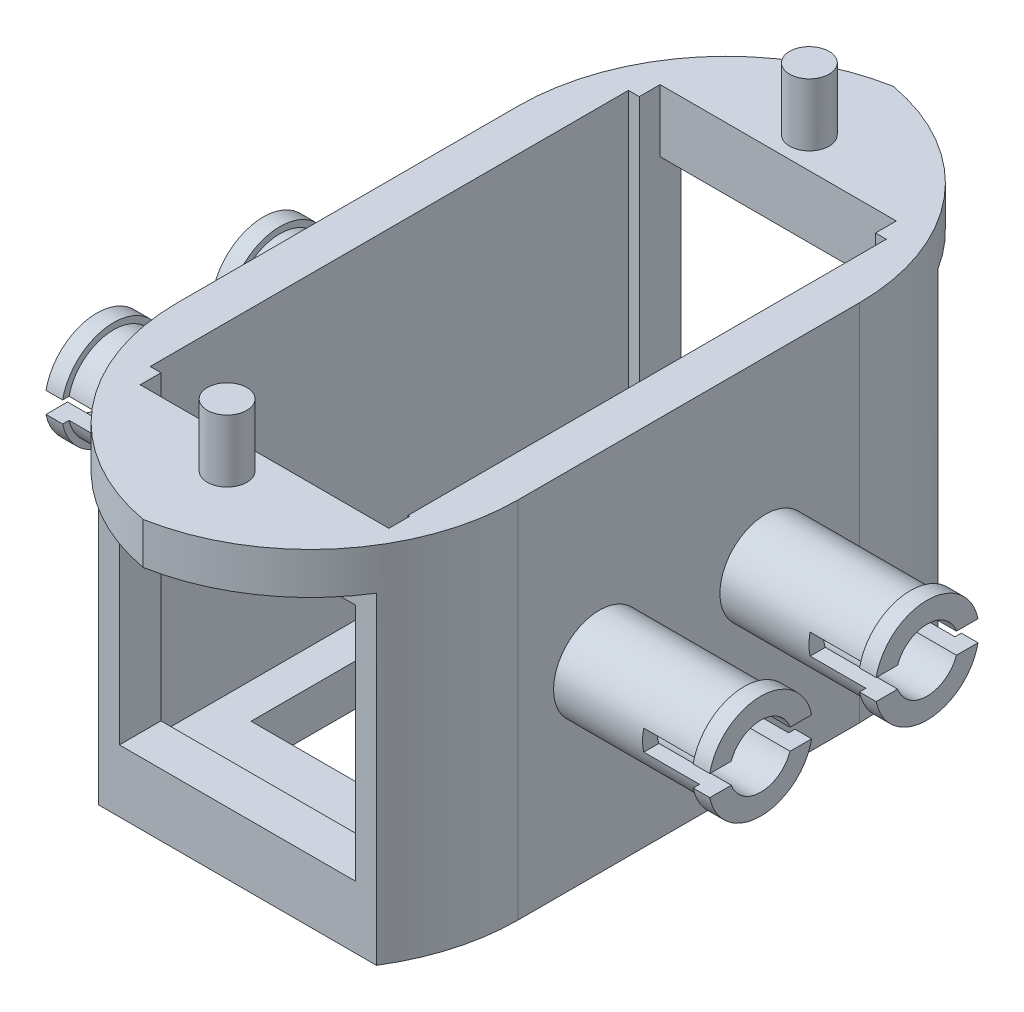
SolidWorks part; units mm, degrees
ref_plane "Front Plane" through (0, 0, 0) normal (0, 0, 1) x (1, 0, 0)
ref_plane "Top Plane" through (0, 0, 0) normal (0, 1, 0) x (1, 0, 0)
ref_plane "Right Plane" through (0, 0, 0) normal (1, 0, 0) x (0, 0, -1)
sketch "Sketch1" plane through (0, 0, 0) normal (0, 1, 0) x (1, 0, 0)
  line L1 (0, 0) -> (16.4, 0)
  line L2 (0, 0) -> (0, 27)
  line L3 (0, 27) -> (16.4, 27)
  line L4 (16.4, 0) -> (16.4, 27)
  dimension "D1" = 16.4
  dimension "D2" = 27
extrude "Boss-Extrude1" add sketch "Sketch1" along normal blind 2
sketch "Sketch4" plane through (0, 2, 0) normal (0, 1, 0) x (1, 0, 0)
  line L0 (0, 27) -> (16.4, 27)
  line L1 (16.4, 27) -> (16.4, 0)
  line L2 (16.4, 0) -> (0, 0)
  line L3 (0, 0) -> (0, 27)
  line L4 (2, 25) -> (14.4, 25)
  line L5 (14.4, 25) -> (14.4, 2)
  line L6 (14.4, 2) -> (2, 2)
  line L7 (2, 2) -> (2, 25)
  line L8 (8.6701, 27) -> (8.6701, 25) construction
  line L9 (14.4, 22.5084) -> (16.4, 22.5084) construction
  line L10 (2, 23.4254) -> (0, 23.4254) construction
  line L11 (9.6577, 2) -> (9.6577, 0) construction
  dimension "D1" = 2
  dimension "D2" = 2
  dimension "D3" = 2
  dimension "D4" = 2
sketch "Sketch5" plane through (0, 2, 0) normal (0, 1, 0) x (1, 0, 0)
  line L0 (0, 27) -> (16.4, 27)
  line L1 (16.4, 27) -> (16.4, 0)
  line L2 (16.4, 0) -> (0, 0)
  line L3 (0, 0) -> (0, 27)
  line L4 (2, 25) -> (2, 2)
  line L5 (2, 2) -> (14.4, 2)
  line L6 (14.4, 2) -> (14.4, 25)
  line L7 (14.4, 25) -> (2, 25)
extrude "Boss-Extrude2" add sketch "Sketch5" along normal blind 15.5
sketch "Sketch6" plane through (0, 0, -27) normal (0, 0, -1) x (-1, 0, 0)
  line L0 (0, 17.5) -> (0, 0) construction
  line L1 (-16.4, 17.5) -> (0, 17.5)
  line L2 (-16.4, 17.5) -> (-16.4, 15.5)
  line L3 (-16.4, 15.5) -> (0, 15.5)
  line L4 (0, 17.5) -> (0, 15.5)
  dimension "D1" = 2
extrude "Boss-Extrude3" add sketch "Sketch6" along normal blind 4.7
sketch "Sketch7" plane through (0, 0, 0) normal (0, 0, 1) x (1, 0, 0)
  line L0 (16.4, 17.5) -> (16.4, 0) construction
  line L1 (0, 17.5) -> (16.4, 17.5)
  line L2 (0, 17.5) -> (0, 15.5)
  line L3 (0, 15.5) -> (16.4, 15.5)
  line L4 (16.4, 17.5) -> (16.4, 15.5)
  dimension "D1" = 2
extrude "Boss-Extrude4" add sketch "Sketch7" along normal blind 4.7
sketch "Sketch8" plane through (0, 17.5, 0) normal (0, 1, 0) x (1, 0, 0)
  line L0 (0, 27.5) -> (16.4, 27.5) construction
  line L1 (0, 31.7) -> (0, -4.7) construction
  line L2 (16.4, -4.7) -> (16.4, 31.7) construction
  line L3 (8.2, 31.7) -> (8.2, 27.5) construction
  line L4 (0, 31.7) -> (16.4, 31.7) construction
  line L5 (0, -0.5) -> (16.4, -0.5) construction
  line L6 (8.2, -4.7) -> (8.2, -0.5) construction
  line L7 (16.4, -4.7) -> (0, -4.7) construction
  line L8 (8.2, -0.5) -> (8.2, 27.5) construction
  circle A0 centre (8.2, 27.5) radius 0.95
  circle A1 centre (8.2, -0.5) radius 0.95
  dimension "D3" = 1.9
  dimension "D4" = 1.9
  dimension "D1" = 4.2
  dimension "D2" = 4.2
extrude "Boss-Extrude5" add sketch "Sketch8" along normal blind 3
fillet "Fillet1" radius 10 4 edges at (16.4, 16.5, -31.7) (0, 16.5, -31.7) (16.4, 16.5, 4.7) (0, 16.5, 4.7)
sketch "Sketch9" plane through (0, 0, 0) normal (-1, 0, 0) x (0, 0, 1)
  line L0 (-7, 8.75) -> (-5.3, 8.75) construction
  line L2 (-17.2, 8.75) -> (-9.2, 8.75) construction
  line L3 (-19.4, 8.75) -> (-21.7, 8.75) construction
  line L4 (-5.3, 0) -> (-5.3, 17.5) construction
  line L5 (-21.7, 17.5) -> (-21.7, 0) construction
  circle A0 centre (-17.2, 8.75) radius 2.2
  circle A1 centre (-9.2, 8.75) radius 2.2
  dimension "D1" = 4.4
  dimension "D3" = 1.7
  dimension "D4" = 8
  dimension "D5" = 8
  dimension "D6" = 2.3
  dimension "D2" = 2
extrude "Boss-Extrude6" add sketch "Sketch9" along normal blind 6.96
sketch "Sketch10" plane through (16.4, 0, 0) normal (1, 0, 0) x (0, 0, -1)
  line L0 (5.3, 8.75) -> (7, 8.75) construction
  line L3 (5.3, 17.5) -> (5.3, 0) construction
  line L4 (21.7, 8.75) -> (20, 8.75) construction
  line L5 (21.7, 0) -> (21.7, 17.5) construction
  line L6 (5.3, 8.75) -> (21.7, 8.75) construction
  circle A0 centre (9.2, 8.75) radius 2.2
  circle A1 centre (17.2, 8.75) radius 2.2
  dimension "D3" = 4.4
  dimension "D1" = 1.7
  dimension "D2" = 1.7
  dimension "D4" = 2
extrude "Boss-Extrude7" add sketch "Sketch10" along normal blind 6.96
sketch "Sketch11" plane through (0, 0, 0) normal (0, 0, 1) x (1, 0, 0)
  line L0 (2.52, 3) -> (13.88, 3)
  line L1 (13.88, 3) -> (13.88, 14.5)
  line L2 (13.88, 14.5) -> (2.52, 14.5)
  line L3 (2.52, 14.5) -> (2.52, 3)
  line L4 (9.3179, 3) -> (9.3179, 2) construction
  line L5 (2, 2) -> (14.4, 2) construction
  line L6 (6.5174, 15.5) -> (6.5174, 14.5) construction
  line L7 (1.52, 15.5) -> (8.2, 15.5) construction
  line L8 (13.88, 10.9411) -> (14.88, 10.9411) construction
  line L9 (14.88, 0) -> (14.88, 15.5) construction
  line L10 (2.52, 11.4187) -> (1.52, 11.4187) construction
  line L11 (1.52, 15.5) -> (1.52, 0) construction
  dimension "D1" = 1
  dimension "D2" = 1
  dimension "D3" = 1
  dimension "D4" = 1
extrude "Cut-Extrude1" cut sketch "Sketch11" against normal through all
sketch "Sketch12" plane through (0, 2, 0) normal (0, 1, 0) x (1, 0, 0)
  line L0 (14.4, 25) -> (2, 2) construction
  line L1 (2, 25) -> (14.4, 2) construction
  line L3 (3.7, 5.1532) -> (12.7, 5.1532)
  line L4 (3.7, 5.1532) -> (3.7, 21.8468)
  line L5 (3.7, 21.8468) -> (12.7, 21.8468)
  line L6 (12.7, 5.1532) -> (12.7, 21.8468)
  line L7 (3.7, 5.1532) -> (12.7, 21.8468) construction
  line L8 (3.7, 21.8468) -> (12.7, 5.1532) construction
  point P8 (8.2, 13.5)
  dimension "D1" = 9
  dimension "D2" = 16.6935
extrude "Cut-Extrude2" cut sketch "Sketch12" against normal blind 10
sketch "Sketch14" plane through (0, 0, -25) normal (0, 0, 1) x (1, 0, 0)
  line L0 (2.52, 14.5) -> (2.52, 17.5)
  line L1 (14.4, 17.5) -> (2, 17.5) construction
  line L4 (13.88, 14.5) -> (2.52, 14.5)
  line L5 (13.88, 14.5) -> (13.88, 17.5)
  line L6 (13.88, 17.5) -> (2.52, 17.5)
extrude "Cut-Extrude5" cut sketch "Sketch14" against normal blind 1
sketch "Sketch15" plane through (0, 0, -2) normal (0, 0, -1) x (-1, 0, 0)
  line L0 (-2, 17.5) -> (-14.4, 17.5) construction
  line L1 (-2.52, 14.5) -> (-14.48, 14.5)
  line L2 (-2.52, 14.5) -> (-2.52, 17.5)
  line L3 (-2.52, 17.5) -> (-14.48, 17.5)
  line L4 (-14.48, 14.5) -> (-14.48, 17.5)
extrude "Cut-Extrude6" cut sketch "Sketch15" against normal blind 1
sketch "Sketch16" plane through (23.36, 0, 0) normal (1, 0, 0) x (0, 0, -1)
  circle A0 centre (9.2, 8.75) radius 2.5
  circle A1 centre (17.2, 8.75) radius 2.5
  dimension "D1" = 5
  dimension "D2" = 5
extrude "Boss-Extrude8" add sketch "Sketch16" along normal blind 0.8
sketch "Sketch17" plane through (-6.96, 0, 0) normal (-1, 0, 0) x (0, 0, 1)
  circle A0 centre (-9.2, 8.75) radius 2.5
  circle A1 centre (-17.2, 8.75) radius 2.5
  dimension "D1" = 5
  dimension "D2" = 5
extrude "Boss-Extrude9" add sketch "Sketch17" along normal blind 0.8
sketch "Sketch18" plane through (-7.76, 0, 0) normal (-1, 0, 0) x (0, 0, 1)
  line L0 (-14.3206, 8.25) -> (-14.3206, 9.25)
  line L1 (-6.2095, 8.75) -> (-6.2095, 8.25)
  line L2 (-6.2095, 8.75) -> (-6.2095, 9.25)
  line L3 (-6.2095, 8.25) -> (-12.1533, 8.25)
  line L4 (-12.1533, 8.25) -> (-12.1533, 9.25)
  line L5 (-12.1533, 9.25) -> (-6.2095, 9.25)
  line L6 (-14.3206, 9.25) -> (-20.4203, 9.25)
  line L7 (-20.4203, 9.25) -> (-20.4203, 8.25)
  line L8 (-20.4203, 8.25) -> (-14.3206, 8.25)
  dimension "D1" = 0.5
  dimension "D2" = 0.5
extrude "Cut-Extrude7" cut sketch "Sketch18" against normal blind 3.48
sketch "Sketch19" plane through (24.16, 0, 0) normal (1, 0, 0) x (0, 0, -1)
  line L1 (6.2972, 8.75) -> (6.2972, 9.25)
  line L2 (6.2972, 8.75) -> (6.2972, 8.25)
  line L3 (6.2972, 9.25) -> (20.3083, 9.25)
  line L4 (20.3083, 9.25) -> (20.3083, 8.25)
  line L5 (20.3083, 8.25) -> (6.2972, 8.25)
  dimension "D1" = 0.5
  dimension "D2" = 0.5
extrude "Cut-Extrude8" cut sketch "Sketch19" against normal blind 3.48
sketch "Sketch20" plane through (24.16, 0, 0) normal (1, 0, 0) x (0, 0, -1)
  circle A0 centre (9.2, 8.75) radius 1.5
  circle A1 centre (17.2, 8.75) radius 1.5
  dimension "D1" = 3
  dimension "D2" = 3
extrude "Cut-Extrude9" cut sketch "Sketch20" against normal blind 7.76
sketch "Sketch21" plane through (-7.76, 0, 0) normal (-1, 0, 0) x (0, 0, 1)
  circle A0 centre (-9.2, 8.75) radius 1.5
  circle A1 centre (-17.2, 8.75) radius 1.5
  dimension "D1" = 3
  dimension "D2" = 3
extrude "Cut-Extrude10" cut sketch "Sketch21" against normal blind 7.76
